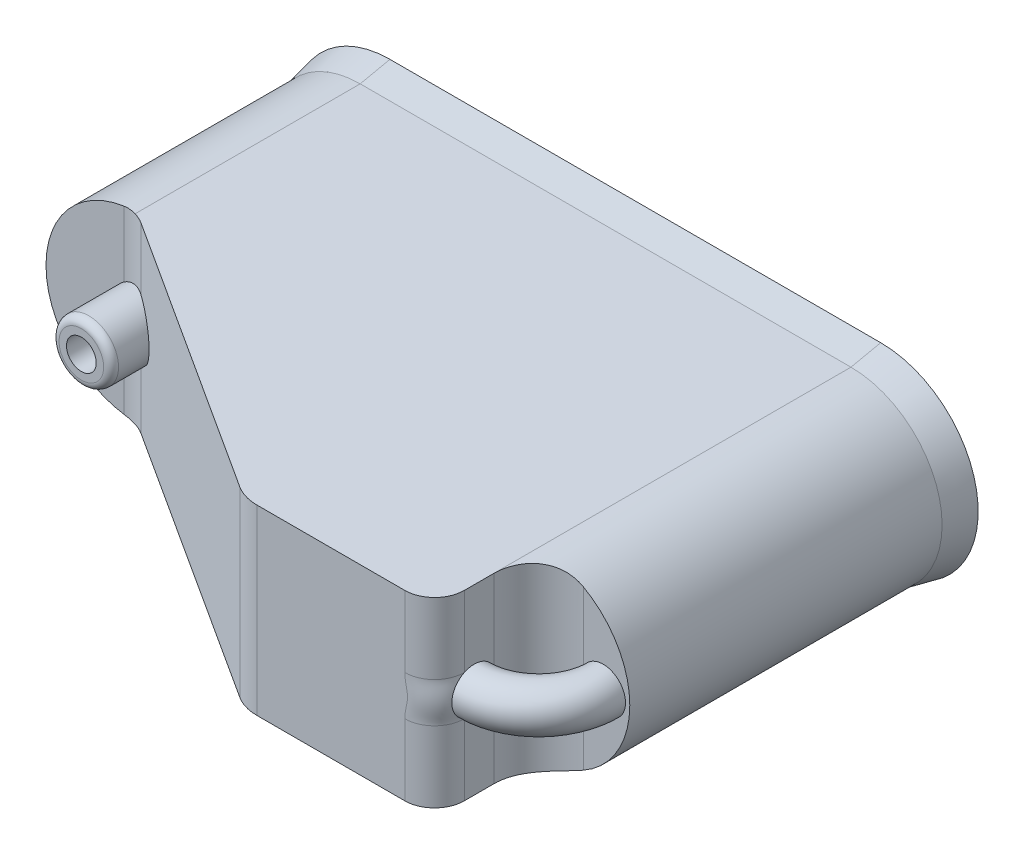
SolidWorks part; units mm, degrees
ref_plane "Front Plane" through (0, 0, 0) normal (0, 0, 1) x (1, 0, 0)
ref_plane "Top Plane" through (0, 0, 0) normal (0, 1, 0) x (1, 0, 0)
ref_plane "Right Plane" through (0, 0, 0) normal (1, 0, 0) x (0, 0, -1)
sketch "Sketch5" plane through (0, 0, 0) normal (0, 1, 0) x (1, 0, 0)
  line L0 (-165, 0) -> (165, 0) construction
  line L1 (-165, 59) -> (165, 59)
  line L2 (-165, 59) -> (-165, -59)
  line L3 (-165, -59) -> (165, -59)
  line L4 (165, 59) -> (165, -59)
  line L5 (-165, 59) -> (165, -59) construction
  line L6 (-165, -59) -> (165, 59) construction
  line L7 (-165, 65.5291) -> (165, 65.5291)
  line L8 (-165, -65.5291) -> (165, -65.5291)
  arc A0 (-165, 65.5291) -> (-165, -65.5291) centre (-165, 0) ccw
  arc A1 (165, -65.5291) -> (165, 65.5291) centre (165, 0) ccw
  point P0 (0, 0)
  point P8 (0, 0)
  dimension "D1" = 118
  dimension "D2" = 330
extrude "Boss-Extrude5" add sketch "Sketch5" along normal blind 20 draft 12 contours A0 L8 A1 L7
sketch "Sketch6" plane through (0, 20, 0) normal (0, 1, 0) x (1, 0, 0)
  line L0 (165, 61.2779) -> (165, -61.2779)
  line L1 (165, 61.2779) -> (36.681, 61.2779)
  line L2 (165, -61.2779) -> (36.681, -61.2779)
  line L3 (36.681, 61.2779) -> (36.681, -61.2779)
extrude "Boss-Extrude6" add sketch "Sketch6" along normal blind 280
sketch "Sketch7" plane through (0, 0, 61.2779) normal (0, 0, 1) x (1, 0, 0)
  line L0 (36.681, 300) -> (36.681, 20)
  line L1 (36.681, 20) -> (-165, 20)
  line L2 (-165, 20) -> (-165, 170)
  line L3 (-165, 170) -> (36.681, 300)
  dimension "D1" = 150
extrude "Boss-Extrude7" add sketch "Sketch7" against normal up to surface (122.5559 mm away) up to face at (100.8405, 160, -61.2779)
sketch "Sketch8" plane through (0, 20, 0) normal (0, 1, 0) x (1, 0, 0)
  line L0 (-165, 61.2779) -> (-165, -61.2779)
  arc A0 (-165, 61.2779) -> (-165, -61.2779) centre (-165, 0) ccw
extrude "Boss-Extrude8" add sketch "Sketch8" along normal blind 150
sketch "Sketch10" plane through (0, 0, 0) normal (0, -1, 0) x (1, 0, 0)
  line L0 (0, 0) -> (162.5, 0)
  circle A0 centre (162.5, 0) radius 10
  dimension "D2" = 20
  dimension "D1" = 162.5
extrude "Boss-Extrude9" add sketch "Sketch10" along normal blind 35 contours A0
sketch "Sketch11" plane through (0, 0, 0) normal (0, -1, 0) x (1, 0, 0)
  line L0 (0, 0) -> (-162.5, 0)
  circle A0 centre (-162.5, 0) radius 10
  dimension "D2" = 20
  dimension "D1" = 162.5
sketch "Sketch13" plane through (0, 0, 0) normal (0, -1, 0) x (1, 0, 0)
  line L0 (-181.9351, 0) -> (-143.0649, 0) construction
  line L1 (0, 0) -> (-162.5, 0) construction
  line L2 (-181.9351, 24.0728) -> (-143.0649, 24.0728)
  line L3 (-181.9351, -24.0728) -> (-143.0649, -24.0728)
  arc A0 (-181.9351, 24.0728) -> (-181.9351, -24.0728) centre (-181.9351, 0) ccw
  arc A1 (-143.0649, -24.0728) -> (-143.0649, 24.0728) centre (-143.0649, 0) ccw
  point P5 (-162.5, 0)
extrude "Boss-Extrude11" add sketch "Sketch13" along normal blind 40
sketch "Sketch14" plane through (0, 0, 0) normal (0, -1, 0) x (1, 0, 0)
  circle A0 centre (-162.5, 0) radius 20
  dimension "D1" = 40
extrude "Boss-Extrude12" add sketch "Sketch14" against normal blind 210
extrude "Cut-Extrude3" cut sketch "Sketch11" against normal up to surface and the other way up to surface contours A0 up to face at (-162.5, 210, -20) other way up to face at (-162.5, -40, 0)
sketch "Sketch15" plane through (0, 20, 0) normal (0, 1, 0) x (1, 0, 0)
  line L0 (165, 61.2779) -> (165, -61.2779)
  arc A0 (165, -61.2779) -> (165, 61.2779) centre (165, 0) ccw
extrude "Boss-Extrude13" add sketch "Sketch15" along normal blind 210
sketch "Sketch16" plane through (165, 0, 0) normal (1, 0, 0) x (0, 0, -1)
  circle A0 centre (0, 273.3956) radius 15
  dimension "D1" = 30
sketch "Sketch17" plane through (0, 0, 61.2779) normal (0, 0, 1) x (1, 0, 0)
  line L0 (165, 258.3956) -> (165, 288.3956) construction
  line L1 (226.2779, 230) -> (165, 230) construction
  arc A0 (165, 273.3956) -> (208.3956, 230) centre (165, 230) cw
sketch "Sketch18" plane through (0, 230, 0) normal (0, 1, 0) x (1, 0, 0)
sweep "Sweep1" add profiles "Sketch16" path "Sketch17"
fillet "Fillet6" radius 30 1 edges at (36.681, 300, 0)
fillet "Fillet7" radius 30 2 edges at (-165, 170, -40.5605) (-165, 170, 40.5605)
fillet "Fillet8" radius 30 1 edges at (165, 230, 0)
fillet "Fillet9" radius 20 1 edges at (165, 300, 0)
fillet "Fillet10" radius 5 1 edges at (-162.5, 210, -20)
sketch "Sketch20" plane through (0, 0, 0) normal (0, -1, 0) x (1, 0, 0)
  point P0 (162.5, 0)
move or copy body "Body-Move/Copy1" bodies to move or copy 117 copy no translate (-162.5, 0, 0)
move or copy body "Body-Move/Copy2" bodies to move or copy 118 copy no rotation origin (0, 0, 0) rotation axis (1, 0, 0) rotation angle 90
sketch "Sketch22" plane through (0, -61.2779, 0) normal (0, -1, 0) x (1, 0, 0)
  text T0 "NGOC_HOAN" font "Century Gothic" height 30
